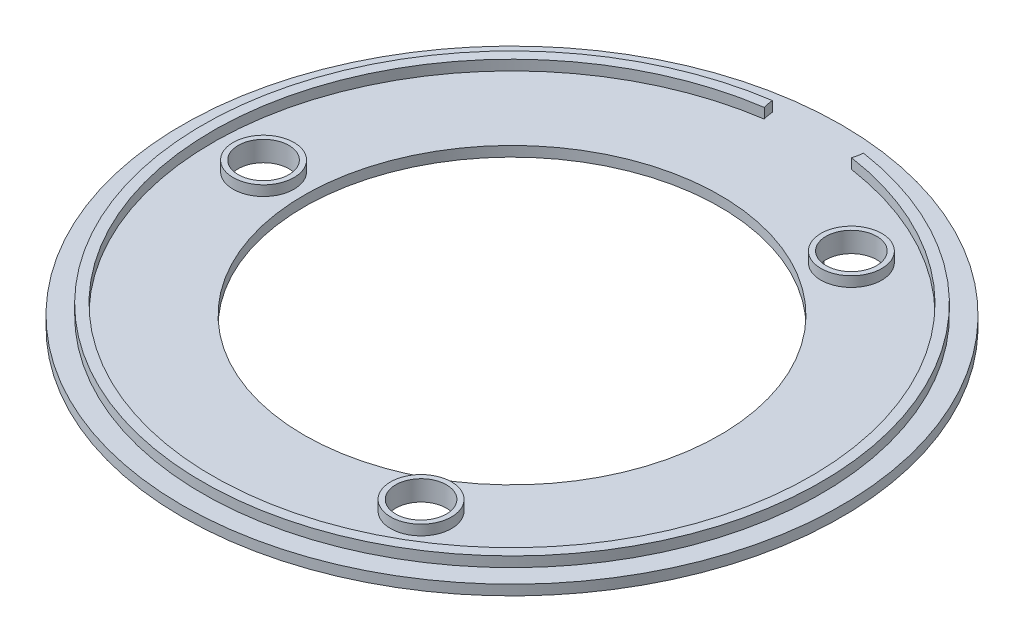
SolidWorks part; units mm, degrees
ref_plane "Alzado" through (0, 0, 0) normal (0, 0, 1) x (1, 0, 0)
ref_plane "Planta" through (0, 0, 0) normal (0, 1, 0) x (1, 0, 0)
ref_plane "Vista lateral" through (0, 0, 0) normal (1, 0, 0) x (0, 0, -1)
sketch "Croquis1" plane through (0, 0, 0) normal (0, 1, 0) x (1, 0, 0)
  circle A0 centre (0, 0) radius 20.5
  circle A1 centre (0, 0) radius 32.5
  dimension "D1" = 41
  dimension "D2" = 65
extrude "Saliente-Extruir1" add sketch "Croquis1" along normal blind 2
sketch "Croquis2" plane through (0, 2, 0) normal (0, 1, 0) x (1, 0, 0)
  circle A0 centre (0, 0) radius 30.5
  circle A1 centre (0, 30.5) radius 4.5
  circle A2 centre (0, 0) radius 32.5
  circle A3 centre (0, 0) radius 29.5
  circle M1 centre (0, 0) radius 32.5
  circle M2 centre (0, 0) radius 20.5
  dimension "D1" = 61
  dimension "D2" = 9
  dimension "D3" = 59
extrude "Cortar-Extruir1" cut sketch "Croquis2" against normal blind 1 contours A1 A0 M1 | A1 A3 M2 | A1 A3 | A0 A1 M1 | A3 A1 A0 region at (23.7937, 2, -20.5161) region at (0, 2, -29.8946) region at (0, 2, -31.3838) region at (21.6995, 2, -18.7344) region at (0, 2, -27.9815)
sketch "Croquis3" plane through (0, 1, 0) normal (0, 1, 0) x (1, 0, 0)
  line L0 (-32.5, 0) -> (0, 0)
  line L1 (15.25, -26.4138) -> (0, 0)
  line L2 (16.25, 28.1458) -> (0, 0)
  line L3 (-29.4659, 0) -> (-28.4659, 0)
  line L4 (-28.4659, 0) -> (-24.5, 0)
  line L5 (15.25, -26.4138) -> (12.25, -21.2176)
  line L6 (14.75, -25.5477) -> (12.25, -21.2176)
  line L7 (14.75, 25.5477) -> (12.25, 21.2176)
  line L8 (-24.5, 0) -> (0, 0)
  circle A0 centre (0, 0) radius 32.5 construction
  arc A1 (-4.4877, 30.168) -> (4.4877, 30.168) centre (0, 0) ccw construction
  circle A2 centre (-24.5, 0) radius 3
  circle A3 centre (-24.5, 0) radius 2.5
  arc A4 (-4.3034, 29.1844) -> (4.3034, 29.1844) centre (0, 0) ccw construction
  circle A5 centre (12.25, -21.2176) radius 3
  circle A6 centre (12.25, -21.2176) radius 2.5
  circle A7 centre (12.25, 21.2176) radius 3
  circle A8 centre (12.25, 21.2176) radius 2.5
  dimension "D6" = 5
  dimension "D8" = 6
  dimension "D9" = 5
  dimension "D11" = 6
  dimension "D12" = 5
  dimension "D4" = 24.5
  dimension "D1" = 120
  dimension "D2" = 120
  dimension "D3" = 120
  dimension "D5" = 24.5
  dimension "D7" = 24.5
extrude "Saliente-Extruir2" add sketch "Croquis3" along normal blind 1 contours A8 L2 A7 L7 | A8 L7 A7 L2 | A6 L1 A5 L6 | A6 L6 A5 L1 | A3 L4 A2 L0 | A3 L0 A2 L4 region at (-24.5, 1, -2.5671) region at (-21.75, 1, 0.0671) region at (9.7141, 1, -22.6817) region at (10.9372, 1, -18.8001) region at (13.7141, 1, 18.6817) region at (10.8128, 1, 18.872)
sketch "Croquis6" plane through (0, 1, 0) normal (0, 1, 0) x (1, 0, 0)
  circle A0 centre (-24.5, 0) radius 2.5
  circle A1 centre (12.25, -21.2176) radius 2.5
  circle A2 centre (12.25, 21.2176) radius 2.5
extrude "Cortar-Extruir2" cut sketch "Croquis6" against normal blind 25 and the other way blind 29
sketch "Croquis7" plane through (0, 0, 0) normal (0, -1, 0) x (1, 0, 0)
  line L0 (-23.5, 0) -> (-23.3077, 3)
  line L1 (-23.3077, 3) -> (-22.8035, 3)
  line L2 (-22.8035, 3) -> (-22.8035, -3)
  line L3 (-22.8035, -3) -> (-23.3077, -3)
  line L4 (-23.3077, -3) -> (-23.5, 0)
  line L5 (12.25, 21.2176) -> (0, 0)
  line L6 (11.75, 20.3516) -> (14.247, 18.6888)
  line L7 (14.247, 18.6888) -> (13.9439, 18.2912)
  line L8 (13.9439, 18.2912) -> (8.8687, 21.2214)
  line L9 (12.25, -21.2176) -> (0, 0)
  line L10 (11.75, -20.3516) -> (14.3612, -18.6012)
  line L11 (8.8687, 21.2214) -> (9.0615, 21.6827)
  line L12 (9.0615, 21.6827) -> (11.75, 20.3516)
  line L13 (14.3612, -18.6012) -> (14.0556, -18.2055)
  line L14 (14.0556, -18.2055) -> (8.8687, -21.2214)
  line L15 (8.8687, -21.2214) -> (9.0615, -21.6827)
  line L16 (9.0615, -21.6827) -> (11.75, -20.3516)
  circle A0 centre (0, 0) radius 20.5
  circle A1 centre (0, 0) radius 23.5
  circle A2 centre (0, 0) radius 23
  dimension "D1" = 47
  dimension "D2" = 46
  dimension "D6" = 3
  dimension "D3" = 3
  dimension "D4" = 3
  dimension "D5" = 3
  dimension "D7" = 6
extrude "Saliente-Extruir3" add sketch "Croquis7" along normal blind 1 contours A2 L11 A1 L1 | A2 L13 A1 L7 | A2 L3 A1 L15 region at (-11.5558, 0, 20.0213) region at (-23.0556, 0, -3.3831) region at (20.7151, 0, 10.2562)
sketch "Croquis8" plane through (0, 1, 0) normal (0, 1, 0) x (1, 0, 0)
  circle A0 centre (0, 0) radius 32.5
